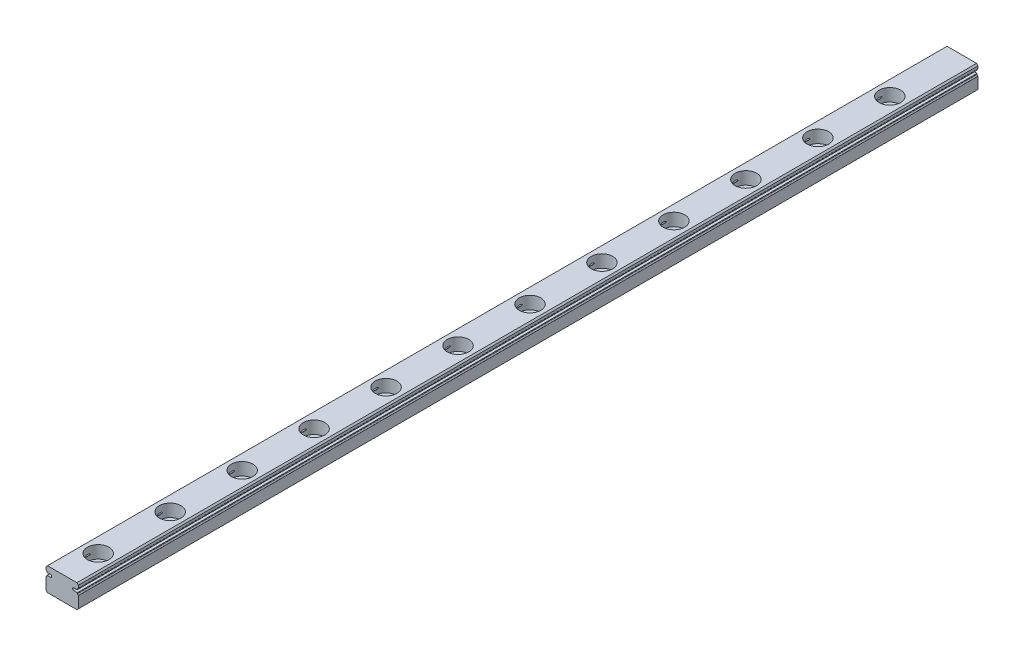
SolidWorks part; units mm, degrees
material "Acero al carbono no aleado"
ref_plane "Alzado" through (0, 0, 0) normal (0, 0, 1) x (1, 0, 0)
ref_plane "Planta" through (0, 0, 0) normal (0, 1, 0) x (1, 0, 0)
ref_plane "Vista lateral" through (0, 0, 0) normal (1, 0, 0) x (0, 0, -1)
ref_plane "Plano1" through (0, 3.3057, 0) normal (0, 1, 0) x (1, 0, 0)
sketch "Croquis1" plane through (0, 3.3057, 0) normal (0, 1, 0) x (1, 0, 0)
  line L0 (4.5, 250) -> (-4.5, 250)
  line L1 (-4.5, 250) -> (-4.5, -250)
  line L2 (-4.5, -250) -> (4.5, -250)
  line L3 (4.5, -250) -> (4.5, 250)
extrude "Saliente-Extruir1" add sketch "Croquis1" against normal blind 6.5
sketch "Croquis2" plane through (0, 0, -250) normal (0, 0, -1) x (-1, 0, 0)
  line L0 (1.6, -3.1943) -> (2.1, -3.1943)
  arc A0 (2.1, -3.1943) -> (1.6, -3.1943) centre (1.85, -3.4568) ccw
extrude "Cortar-Extruir1" cut sketch "Croquis2" against normal through all
sketch "Croquis3" plane through (0, 0, -250) normal (0, 0, -1) x (-1, 0, 0)
  line L0 (-4.5, 1.6457) -> (-4.5, 0.9457)
  line L1 (-4.5, 0.9457) -> (-3.25, 0.9457)
  line L2 (-3.25, 1.6457) -> (-4.5, 1.6457)
  arc A0 (-3.25, 0.9457) -> (-3.25, 1.6457) centre (-3.25, 1.2957) ccw
extrude "Cortar-Extruir2" cut sketch "Croquis3" against normal through all
sketch "Croquis4" plane through (0, 0, -250) normal (0, 0, -1) x (-1, 0, 0)
  line L0 (-4.3353, 0.9457) -> (-4.5, 0.9457)
  line L1 (-4.5, 0.9457) -> (-4.5, 0.4169)
  arc A0 (-4.5, 0.4169) -> (-4.3353, 0.9457) centre (-4.622, 0.745) ccw
extrude "Cortar-Extruir3" cut sketch "Croquis4" against normal through all
sketch "Croquis5" plane through (0, 0, -250) normal (0, 0, -1) x (-1, 0, 0)
  line L0 (-4.5, 2.1744) -> (-4.5, 1.6457)
  line L1 (-4.5, 1.6457) -> (-4.3353, 1.6457)
  arc A0 (-4.3353, 1.6457) -> (-4.5, 2.1744) centre (-4.622, 1.8464) ccw
extrude "Cortar-Extruir4" cut sketch "Croquis5" against normal through all
sketch "Croquis6" plane through (0, 0, -250) normal (0, 0, -1) x (-1, 0, 0)
  line L0 (4.5, 0.9457) -> (4.5, 1.6457)
  line L1 (4.5, 1.6457) -> (3.25, 1.6457)
  line L2 (3.25, 0.9457) -> (4.5, 0.9457)
  arc A0 (3.25, 1.6457) -> (3.25, 0.9457) centre (3.25, 1.2957) ccw
extrude "Cortar-Extruir5" cut sketch "Croquis6" against normal through all
sketch "Croquis7" plane through (0, 0, -250) normal (0, 0, -1) x (-1, 0, 0)
  line L0 (4.3353, 1.6457) -> (4.5, 1.6457)
  line L1 (4.5, 1.6457) -> (4.5, 2.1744)
  arc A0 (4.5, 2.1744) -> (4.3353, 1.6457) centre (4.622, 1.8464) ccw
extrude "Cortar-Extruir6" cut sketch "Croquis7" against normal through all
sketch "Croquis8" plane through (0, 0, -250) normal (0, 0, -1) x (-1, 0, 0)
  line L0 (4.5, 0.4169) -> (4.5, 0.9457)
  line L1 (4.5, 0.9457) -> (4.3353, 0.9457)
  arc A0 (4.3353, 0.9457) -> (4.5, 0.4169) centre (4.622, 0.745) ccw
extrude "Cortar-Extruir7" cut sketch "Croquis8" against normal through all
hole_wizard "Refrentado para tornillo con cabeza hexagonal de M31" positions "Croquis10" profile "Croquis9" counterbore size "M3" standard "Ansi Metric"
sketch "Croquis10" plane through (0, 3.3057, 0) normal (0, 1, 0) x (1, 0, 0)
  point P0 (0, -240)
  point P1 (0, -220)
  point P2 (0, -200)
  point P3 (0, -180)
  point P4 (0, -160)
  point P5 (0, -140)
  point P6 (0, -120)
  point P7 (0, -100)
  point P8 (0, -80)
  point P9 (0, -60)
  point P10 (0, -40)
  point P11 (0, -20)
sketch "Croquis9" plane through (0, 3.3057, 240) normal (1, 0, 0) x (0, 0, 1)
  line L0 (0, 0) -> (0, 6.5)
  line L1 (0, 6.5) -> (1.75, 6.5)
  line L3 (1.75, 6.5) -> (1.75, 3.5)
  line L4 (1.75, 3.5) -> (3, 3.5)
  line L5 (3, 3.5) -> (3, 0)
  line L7 (3, 0) -> (0, 0)
  line L11 (0, -6.35) -> (0, 107.95) construction
  dimension "Diámetro de taladro hasta el siguiente" = 3.5
  dimension "Profundidad de taladro hasta el siguiente" = 6.5
  dimension "Diámetro de refrentado" = 6
  dimension "Profundidad de refrentado" = 3.5
chamfer "Chaflán1" distance 0.4 angle 45 4 edges at (-4.5, -3.1943, 0) (-4.5, 3.3057, 0) (4.5, -3.1943, 0) (4.5, 3.3057, 0)
chamfer "Chaflán2" distance 0.011 angle 36.529 4 edges at (-4.5, 2.1744, 0) (4.5, 0.4169, 0) (-4.5, 0.4169, 0) (4.5, 2.1744, 0) first distance on face at (-4.3528, 1.9303, 0) first distance on face at (4.3528, 0.6611, 0) first distance on face at (-4.5, -1.1887, 0) first distance on face at (4.5, 2.5401, 0)
chamfer "Chaflán3" distance 0.151 angle 53.471 4 edges at (-4.3353, 0.9457, 0) (4.3353, 0.9457, 0) (-4.3353, 1.6457, 0) (4.3353, 1.6457, 0) first distance on face at (-3.7926, 0.9457, 0) first distance on face at (4.3493, 0.6648, 0) first distance on face at (-4.3493, 1.9266, 0) first distance on face at (3.7926, 1.6457, 0)
sketch "Croquis11" plane through (0, 0, -250) normal (0, 0, -1) x (-1, 0, 0)
  line L1 (14.2088, 12.0295) -> (-12.4492, 12.0295)
  line L2 (14.2088, 12.0295) -> (14.2088, -16.4151)
  line L3 (14.2088, -16.4151) -> (-12.4492, -16.4151)
  line L4 (-12.4492, 12.0295) -> (-12.4492, -16.4151)
extrude "Cortar-Extruir8" cut sketch "Croquis11" against normal blind 250
